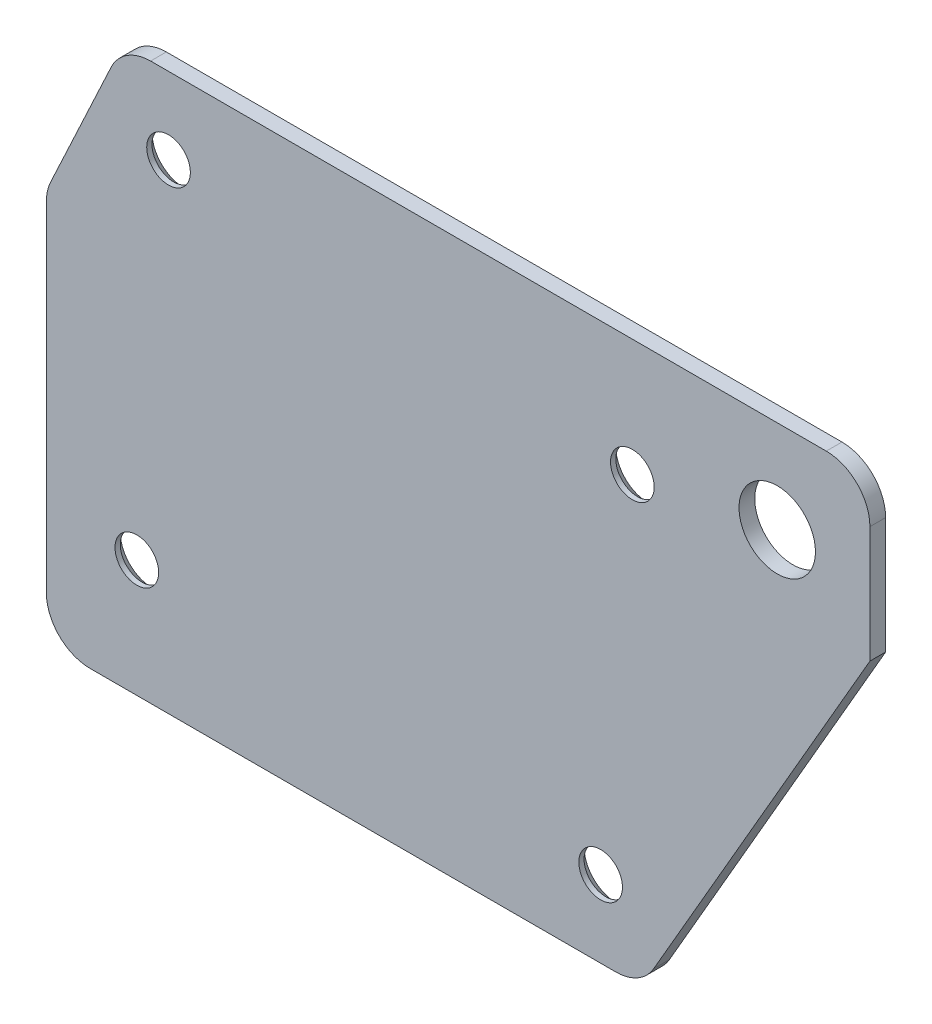
SolidWorks part; units mm, degrees
material "ASTM A36 Steel"
ref_plane "Front Plane" through (0, 0, 0) normal (0, 0, 1) x (1, 0, 0)
ref_plane "Top Plane" through (0, 0, 0) normal (0, 1, 0) x (1, 0, 0)
ref_plane "Right Plane" through (0, 0, 0) normal (1, 0, 0) x (0, 0, -1)
sketch "Sketch11" plane through (0, 0, 0) normal (0, 0, 1) x (1, 0, 0)
  line L0 (-49.2252, 40.4876) -> (-49.2252, -40.4876)
  line L1 (-49.2252, -40.4876) -> (37.338, -40.4876)
  line L2 (37.338, -40.4876) -> (70.6374, 17.1887)
  line L4 (70.6374, 40.4876) -> (70.6374, 17.1887)
  line L5 (70.6374, 40.4876) -> (-49.2252, 40.4876)
  circle A0 centre (57.15, 27.0002) radius 12.7 construction
  circle A1 centre (0, 0) radius 48.5 construction
  circle A2 centre (57.15, 27.0002) radius 5.5626
  dimension "D11" = 25.4
  dimension "D12" = 97
  dimension "D13" = 11.1252
  dimension "D2" = 60
  dimension "D8" = 27.0002
  dimension "D15" = 57.15
  dimension "D3" = 40.4876
  dimension "D4" = 40.4876
  dimension "D9" = 70.6374
  dimension "D14" = 49.2252
  dimension "D16" = 16.5862
sheet metal parameters "Sheet-Metal1" thickness 2.286 parameters "D1"=1.143
base flange "Base-Flange1" sketch "Sketch11" thickness 2.286 reverse thickness direction no parameters "D1"=1.143
hole_wizard "CSK for M4 FH Modified" positions "Sketch16" profile "Sketch15" countersink size "M4" standard "Ansi Metric" end condition through all
sketch "Sketch16" plane through (-9.7442, -24.2896, -2.286) normal (0, 0, 1) x (1, 0, 0)
  line L0 (9.7442, 24.2896) -> (35.1442, 24.2896) construction
  line L1 (9.7442, 24.2896) -> (-8.8321, 41.6124) construction
  line L2 (9.7442, 24.2896) -> (-15.6558, 24.2896) construction
  line L3 (9.7442, 24.2896) -> (-11.558, 10.4558) construction
  circle A0 centre (9.7442, 24.2896) radius 43 construction
  circle A1 centre (9.7442, 24.2896) radius 48.5 construction
  point P1 (45.8071, 47.7091)
  point P3 (-21.704, 53.6156)
  point P7 (-26.3186, 0.8702)
  point P9 (41.1925, -5.0363)
  dimension "D1" = 86
  dimension "D5" = 97
  dimension "D2" = 25.4
  dimension "D3" = 43
  dimension "D4" = 33
sketch "Sketch15" plane through (36.0628, 23.4195, -2.286) normal (1, 0, 0) x (0, 1, 0)
  line L0 (0, 0) -> (0, 2.286)
  line L1 (0, 2.286) -> (3.175, 2.286)
  line L2 (3.175, 2.286) -> (3.175, 1.524)
  line L3 (3.175, 1.524) -> (4.699, 0)
  line L5 (4.699, 0) -> (0, 0)
  line L6 (-3.175, 1.524) -> (-4.699, 0) construction
  line L11 (0, -6.35) -> (0, 107.95) construction
  dimension "Thru Hole Dia." = 6.35
  dimension "Thru Hole Depth" = 2.286
  dimension "Near C'Sink Dia." = 9.398
  dimension "Near C'Sink Angle" = 90
sketch "Sketch17" plane through (0, 0, 0) normal (0, 0, 1) x (1, 0, 0)
  line L0 (-34.5467, 48.1076) -> (-56.8452, 0.2884)
  line L1 (-56.8452, 0.2884) -> (-56.8452, 48.1076)
  line L2 (-56.8452, 48.1076) -> (-34.5467, 48.1076)
  line L3 (70.6374, 40.4876) -> (-49.2252, 40.4876) construction
  line L4 (-49.2252, 40.4876) -> (-49.2252, -40.4876) construction
  point P2 (-38.1, 40.4876)
  dimension "D1" = 11.1252
  dimension "D2" = 25
  dimension "D3" = 7.62
  dimension "D4" = 7.62
extrude "Cut-Extrude1" cut sketch "Sketch17" against normal through all normal cut yes
fillet "Fillet1" radius 6.35 5 edges at (70.6374, 40.4876, -1.143) (37.338, -40.4876, -1.143) (-49.2252, -40.4876, -1.143) (-38.1, 40.4876, -1.143) (-49.2252, 16.6295, -1.143)
flat pattern "Flat-Pattern1"
sketch "Bend-Lines1" plane through (0, 0, -2.286) normal (0, 0, -1) x (-1, 0, 0)
  point P0 (-8.9048, -97.3949)
  point P1 (40.6548, -97.3949)
